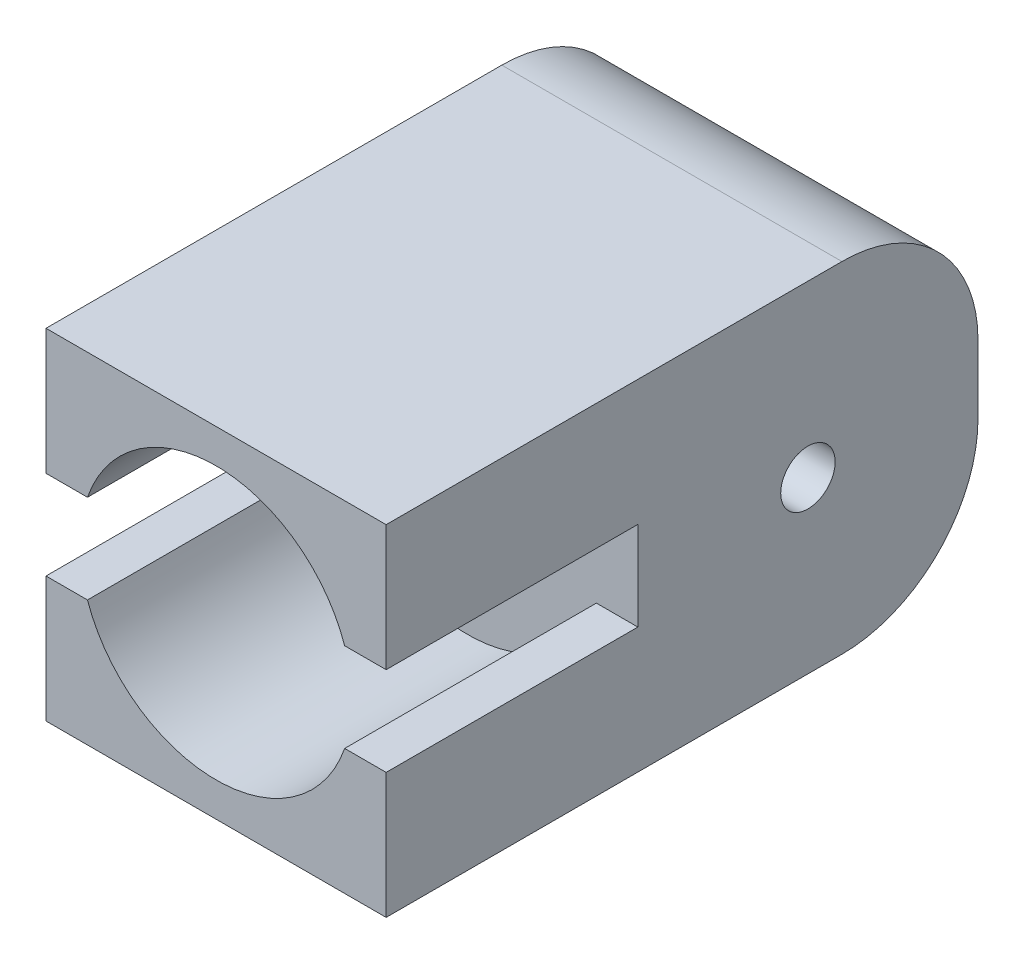
SolidWorks part; units mm, degrees
ref_plane "정면" through (0, 0, 0) normal (0, 0, 1) x (1, 0, 0)
ref_plane "윗면" through (0, 0, 0) normal (0, 1, 0) x (1, 0, 0)
ref_plane "우측면" through (0, 0, 0) normal (1, 0, 0) x (0, 0, -1)
sketch "스케치1" plane through (0, 0, 0) normal (0, 0, 1) x (1, 0, 0)
  line L0 (0, 0) -> (-22.1607, 0) construction
  line L1 (-25, 6.535) -> (25, 6.535)
  line L2 (-25, 6.535) -> (-25, 25)
  line L3 (-25, 25) -> (25, 25)
  line L4 (25, 25) -> (25, 6.535)
  line L5 (0, 25) -> (0, 0) construction
  line L6 (-25, -6.535) -> (-25, -25)
  line L7 (-25, -25) -> (25, -25)
  line L8 (25, -25) -> (25, -6.535)
  line L9 (-25, -6.535) -> (25, -6.535)
  line L11 (-25, 25) -> (25, 25)
  line L12 (-25, 25) -> (-25, -25)
  line L13 (-25, -25) -> (25, -25)
  line L14 (25, 25) -> (25, -25)
  circle A0 centre (0, 0) radius 20
  point P4 (-29.5387, 5)
  dimension "D1" = 5
  dimension "D2" = 40
  dimension "D3" = 25
extrude "보스-돌출1" add sketch "스케치1" along normal blind 37 contours A0 L1 L4 L3 L2 | A0 L9 L6 L7 L8 region at (-24.467, 15.7675, 0) region at (-21.9511, -7.068, 0)
extrude "보스-돌출2" add sketch "스케치1<4>" against normal blind 50 contours A0 L1 L4 L3 L2 | L1 A0 | L1 A0 L9 | A0 L1 L12 L9 | A0 L9 L14 L1 | L9 A0 | A0 L9 L6 L7 L8 region at (-24.467, 15.7675, 0) region at (-22.3092, 0, 0) region at (0, 12.1148, 0) region at (0, 0, 0) region at (-21.9511, -7.068, 0) region at (22.3092, 0, 0) region at (0, -12.1148, 0)
sketch "스케치1<4>" plane through (0, 0, 0) normal (0, 0, 1) x (1, 0, 0) same geometry as "스케치1"
sketch "스케치3" plane through (-25, 0, 0) normal (-1, 0, 0) x (0, 0, 1)
  line L0 (-50, -25) -> (-50, 25) construction
  line L1 (-50, 0) -> (0, 0) construction
  line L2 (0, -6.535) -> (0, 6.535) construction
  circle A0 centre (-25, 0) radius 4
  point P0 (-50, 0)
extrude "컷-돌출1" cut sketch "스케치3" against normal blind 54
fillet "필렛1" radius 20 2 edges at (0, -25, -50) (0, 25, -50)
